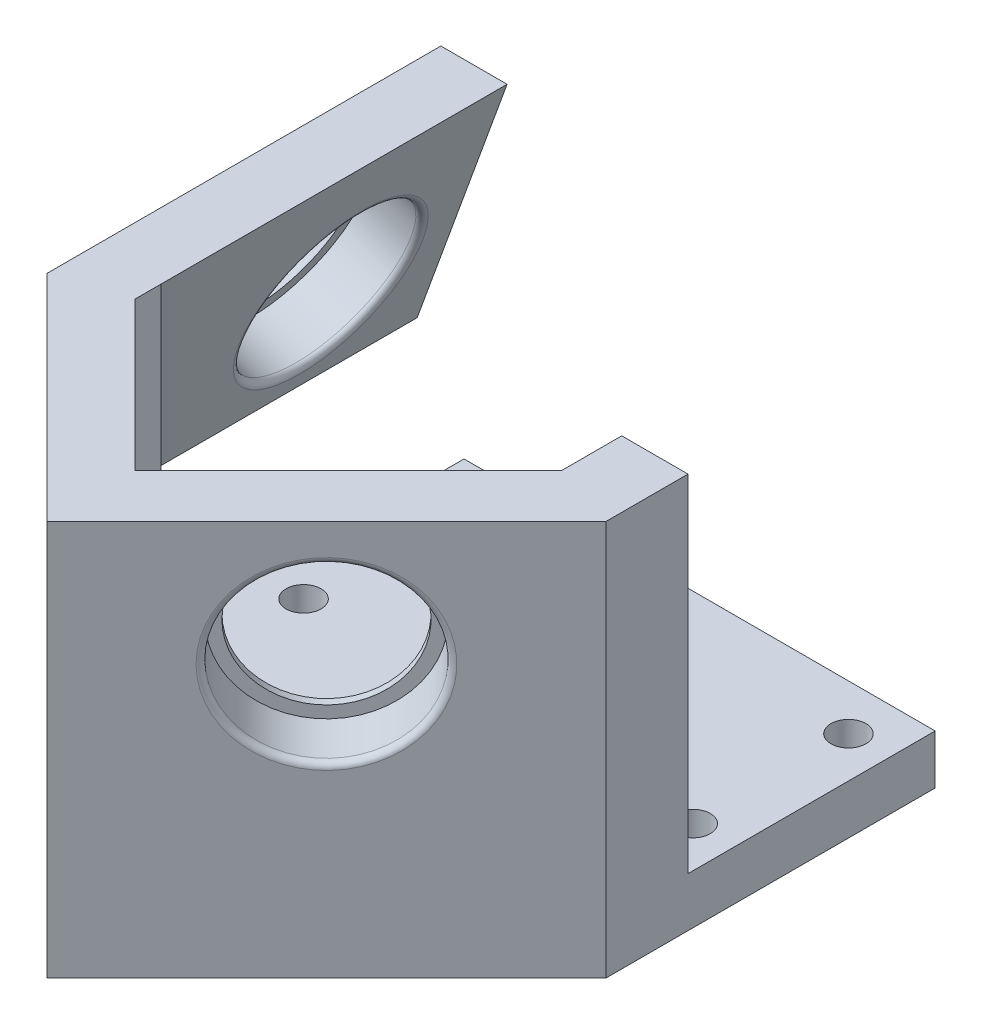
SolidWorks part; units mm, degrees
ref_plane "Front Plane" through (0, 0, 0) normal (0, 0, 1) x (1, 0, 0)
ref_plane "Top Plane" through (0, 0, 0) normal (0, 1, 0) x (1, 0, 0)
ref_plane "Right Plane" through (0, 0, 0) normal (1, 0, 0) x (0, 0, -1)
sketch "Sketch1" plane through (0, 0, 0) normal (0, 1, 0) x (1, 0, 0)
  line L0 (-35.921, 0) -> (0, 35.921)
  line L1 (-35.921, 0) -> (0, -35.921)
  line L2 (0, 35.921) -> (35.921, 0)
  line L3 (0, -35.921) -> (35.921, 0)
  line L4 (-35.921, 0) -> (35.921, 0) construction
  line L5 (0, 35.921) -> (0, -35.921) construction
  point P1 (0, 0)
  dimension "D1" = 50.8
  dimension "D2" = 50.8
extrude "Boss-Extrude1" add sketch "Sketch1" along normal mid plane 31.75
sketch "Sketch2" plane through (17.9605, 0, 17.9605) normal (0.7071, 0, 0.7071) x (0.7071, 0, -0.7071)
  circle A0 centre (0, 0) radius 11.05
  dimension "D1" = 22.1
extrude "Cut-Extrude1" cut sketch "Sketch2" against normal blind 8
sketch "Sketch3" plane through (-17.9605, 0, 17.9605) normal (-0.7071, 0, 0.7071) x (0.7071, 0, 0.7071)
  circle A0 centre (0, 0) radius 11.05
  dimension "D1" = 22.1
extrude "Cut-Extrude2" cut sketch "Sketch3" against normal blind 8
sketch "Sketch4" plane through (0, 15.875, 0) normal (0, 1, 0) x (1, 0, 0)
  line L0 (25.4, 10.521) -> (-25.4, 10.521)
  line L1 (35.921, 0) -> (0, 35.921) construction
  line L2 (0, 35.921) -> (-35.921, 0) construction
  line L3 (-25.4, 10.521) -> (0, 35.921)
  line L4 (0, 35.921) -> (25.4, 10.521)
  dimension "D1" = 25.4
extrude "Cut-Extrude3" cut sketch "Sketch4" against normal through all
sketch "Sketch5" plane through (0, 0, -10.521) normal (0, 0, -1) x (-1, 0, 0)
  line L0 (-35.921, 15.875) -> (-35.921, -15.875)
  line L1 (-35.921, -15.875) -> (39.135, -15.875)
  line L2 (39.135, -15.875) -> (27.579, 15.875)
  line L3 (27.579, 15.875) -> (-35.921, 15.875)
  line L4 (25.4, -15.875) -> (-25.4, -15.875) construction
  line L5 (-35.921, 15.875) -> (-35.921, -15.875) construction
  line L8 (25.4, 15.875) -> (-25.4, 15.875) construction
  point P6 (0, 0)
  dimension "D1" = 70
  dimension "D2" = 63.5
extrude "Boss-Extrude2" add sketch "Sketch5" against normal up to surface and the other way blind 31.75 up to face at (30.6605, 0, -5.2605)
sketch "Sketch6" plane through (-29.455, 10.7207, 0) normal (-0.9397, 0.342, 0) x (0, 0, 1)
  line L0 (-42.271, -28.3026) -> (-42.271, 5.4851) construction
  line L1 (-42.271, -28.3026) -> (-10.521, -28.3026) construction
  circle A0 centre (-26.396, -11.4088) radius 11.05
  point P4 (-42.271, -11.4088)
  point P7 (-26.396, -28.3026)
  dimension "D1" = 22.1
extrude "Cut-Extrude4" cut sketch "Sketch6" against normal through all
sketch "Sketch7" plane through (0, 0, -42.271) normal (0, 0, -1) x (-1, 0, 0)
  line L1 (-35.921, -15.875) -> (39.135, -15.875) construction
  line L3 (19.0656, 15.875) -> (30.6216, -15.875)
  line L4 (-35.921, -15.875) -> (30.6216, -15.875)
  line L5 (39.135, -15.875) -> (27.579, 15.875) construction
  line L6 (27.579, 15.875) -> (-35.921, 15.875) construction
  line L7 (-35.921, -15.875) -> (-35.921, 15.875)
  line L8 (-35.921, 15.875) -> (19.0656, 15.875)
  dimension "D3" = 8
extrude "Cut-Extrude5" cut sketch "Sketch7" against normal blind 31.75
sketch "Sketch8" plane through (0, 15.875, 0) normal (0, 1, 0) x (1, 0, 0)
  line L5 (-42.1413, -6.2203) -> (-8.2965, -39.8855)
  line L6 (0, -35.921) -> (0, -57.0039)
  line L13 (0, -57.0039) -> (-46.5861, -10.6651)
  line L14 (-46.5861, -10.6651) -> (-42.1413, -6.2203)
  line L15 (-8.2965, -39.8855) -> (-8.2965, -27.6245)
  line L16 (-35.921, 0) -> (0, -35.921) construction
  line L17 (-8.2965, -27.6245) -> (0, -35.921)
  line L18 (-25.4, 10.521) -> (-35.921, 0) construction
extrude "Boss-Extrude3" [suppressed] add sketch "Sketch8" against normal up to surface (25.4 mm away) up to face at (2.1042, -15.875, 2.9758)
sketch "Sketch9" plane through (0, -15.875, 0) normal (0, -1, 0) x (1, 0, 0)
  line L0 (-25.4, -10.521) -> (-35.921, 0)
  line L1 (-35.921, 0) -> (-46.442, -10.521)
  line L2 (-46.442, -10.521) -> (-25.4, -10.521)
  line L3 (-35.921, 0) -> (0, 35.921) construction
extrude "Boss-Extrude4" add sketch "Sketch9" against normal up to surface (31.75 mm away) up to face at (-9.1964, 15.875, -10.0783)
sketch "Sketch10" plane through (0, 0, -42.271) normal (0, 0, -1) x (-1, 0, 0)
  line L0 (39.135, -15.875) -> (27.579, 15.875) construction
  line L1 (39.135, -15.875) -> (27.579, 15.875)
  line L6 (27.579, 15.875) -> (39.135, -15.875)
  line L7 (39.135, -15.875) -> (46.442, -15.875)
  line L8 (46.442, -15.875) -> (46.442, 15.875)
  line L9 (46.442, 15.875) -> (27.579, 15.875)
  line L10 (27.579, 15.875) -> (39.135, -15.875)
  line L11 (39.135, -15.875) -> (46.442, -15.875)
  line L12 (46.442, -15.875) -> (46.442, 15.875)
  line L13 (46.442, 15.875) -> (27.579, 15.875)
  line M7 (39.135, -15.875) -> (27.579, 15.875)
  dimension "D1" = 0
extrude "Cut-Extrude6" cut sketch "Sketch10" against normal through all contours L12 L13 L11 M7 region at (-39.4743, 2.3367, -42.271)
sketch "Sketch11" plane through (0, -15.875, 0) normal (0, -1, 0) x (1, 0, 0)
  line L3 (-30.6216, -10.521) -> (-39.135, -10.521)
  line L4 (-39.135, -42.271) -> (-39.135, -3.214) construction
  line L5 (-39.135, -10.521) -> (-39.135, -3.214)
  line L10 (0, 35.921) -> (-39.135, -3.214)
  line L11 (-39.135, -3.214) -> (-39.135, -42.271)
  line L12 (-39.135, -42.271) -> (-30.6216, -42.271)
  line L13 (-30.6216, -42.271) -> (-30.6216, -10.521)
  line L21 (-30.6216, -10.521) -> (35.921, -10.521)
  line L22 (35.921, -10.521) -> (35.921, 0)
  line L23 (35.921, 0) -> (0, 35.921)
  line L24 (0, 35.921) -> (-39.135, -3.214)
  line L29 (-30.6216, -10.521) -> (35.921, -10.521)
  line L30 (35.921, -10.521) -> (35.921, 0)
  line L31 (35.921, 0) -> (0, 35.921)
  dimension "D1" = 0
extrude "Boss-Extrude5" add sketch "Sketch11" along normal blind 12.7
sketch "Sketch12" plane through (0, -28.575, 0) normal (0, -1, 0) x (1, 0, 0)
  line L0 (35.921, -10.521) -> (35.921, 0)
  line L1 (35.921, 0) -> (0, 35.921)
  line L2 (0, 35.921) -> (-39.135, -3.214)
  line L3 (-39.135, -3.214) -> (-39.135, -42.271)
  line L4 (-39.135, -42.271) -> (35.921, -42.271)
  line L5 (35.921, -42.271) -> (35.921, -10.521)
extrude "Boss-Extrude6" add sketch "Sketch12" along normal blind 6.35
sketch "Sketch14" plane through (0, 0, -10.521) normal (0, 0, -1) x (-1, 0, 0)
  line L0 (35.244, -28.575) -> (19.0656, 15.875)
  line L1 (39.135, -34.925) -> (26.3581, -34.925)
  line L2 (19.0656, 15.875) -> (8.4238, 15.875)
  line L3 (24.6023, -28.575) -> (8.4238, 15.875)
  line L4 (19.0656, 15.875) -> (-35.921, 15.875) construction
  line L5 (30.6216, -15.875) -> (19.0656, 15.875) construction
  line L6 (39.135, -34.925) -> (-35.921, -34.925) construction
  line L7 (39.135, -34.925) -> (39.135, -28.575)
  line L8 (39.135, -28.575) -> (35.244, -28.575)
  line L9 (24.6023, -28.575) -> (24.6023, -34.925)
  line L10 (24.6023, -34.925) -> (26.3581, -34.925)
  line L11 (39.135, -28.575) -> (-35.921, -28.575) construction
  dimension "D1" = 10
extrude "Cut-Extrude7" cut sketch "Sketch14" along normal through all
sketch "Sketch15" plane through (0, -34.925, 0) normal (0, -1, 0) x (1, 0, 0)
  line L0 (-24.6023, -42.271) -> (35.921, -42.271) construction
  line L1 (30.6594, -16.396) -> (-19.3406, -16.396) construction
  line L2 (30.6594, -16.396) -> (30.6594, -36.396) construction
  line L3 (30.6594, -36.396) -> (-19.3406, -36.396) construction
  line L4 (-19.3406, -16.396) -> (-19.3406, -36.396) construction
  line L5 (30.6594, -16.396) -> (-19.3406, -36.396) construction
  line L6 (30.6594, -36.396) -> (-19.3406, -16.396) construction
  line L9 (-24.6023, -42.271) -> (-24.6023, -10.521) construction
  circle A0 centre (30.6594, -36.396) radius 2.25
  circle A1 centre (30.6594, -16.396) radius 2.25
  circle A2 centre (-19.3406, -16.396) radius 2.25
  circle A3 centre (-19.3406, -36.396) radius 2.25
  point P0 (5.6594, -26.396)
  point P11 (5.6594, -42.271)
  point P14 (-24.6023, -26.396)
  dimension "D1" = 4.5
  dimension "D2" = 50
  dimension "D3" = 20
extrude "Cut-Extrude8" cut sketch "Sketch15" against normal up to next
sketch "Sketch22" plane through (-29.455, 10.7207, 0) normal (-0.9397, 0.342, 0) x (0, 0, 1)
  circle A0 centre (-26.396, -11.4088) radius 9.5
  circle A1 centre (-26.396, -11.4088) radius 11.05 construction
  circle A2 centre (-26.396, -11.4088) radius 11.05
  dimension "D1" = 19
extrude "Boss-Extrude10" add sketch "Sketch22" against normal offset from surface (1 mm away) 7 up to face at (-24.8436, 0, -26.396)
fillet "Fillet1" radius 0.7937 3 edges at (25.774, 0, 10.147) (-10.147, 0, 25.774) (-29.6188, -13.1198, -26.396)
sketch "Sketch17" plane through (0, 15.875, 0) normal (0, 1, 0) x (1, 0, 0)
  line L0 (-19.0656, 10.521) -> (-19.0656, -5.5418)
  line L1 (-19.0656, -5.5418) -> (0, -24.6073)
  line L2 (0, -24.6073) -> (27.4076, 2.8003)
  line L3 (27.4076, 2.8003) -> (27.4076, 10.521)
  line L4 (-19.0656, 10.521) -> (35.921, 10.521) construction
  line L5 (13.7038, -10.9035) -> (19.3607, -16.5604) construction
  line L6 (0, -35.921) -> (35.921, 0) construction
  line L7 (-9.5328, -15.0745) -> (-15.1896, -20.7314) construction
  line L8 (-27.579, -8.342) -> (0, -35.921) construction
  line L9 (27.4076, 10.521) -> (35.921, 10.521) construction
  line L10 (-19.0656, 10.521) -> (-27.579, 10.521) construction
  line L11 (-27.579, 42.271) -> (-27.579, -8.342) construction
  line L12 (-19.0656, 10.521) -> (27.4076, 10.521)
  dimension "D1" = 8
extrude "Cut-Extrude9" cut sketch "Sketch17" against normal up to surface (44.45 mm away) up to face at (-19.3406, -28.575, -34.146)
sketch "Sketch18" plane through (-12.3037, 0, 12.3037) normal (0.7071, 0, -0.7071) x (-0.7071, 0, -0.7071)
  circle A0 centre (0, 0) radius 9.5
  arc A1 (9.5628, 5.5368) -> (9.5628, -5.5368) centre (0, 0) ccw construction
  arc A2 (9.5628, 5.5368) -> (9.5628, -5.5368) centre (0, 0) ccw
  arc A3 (9.5628, 5.5368) -> (9.5628, -5.5368) centre (0, 0) cw
  dimension "D1" = 19
extrude "Boss-Extrude8" add sketch "Sketch18" against normal offset from surface (1 mm away) 7 up to face at (-26.3353, 0, 9.5857)
sketch "Sketch19" plane through (12.3037, 0, 12.3037) normal (-0.7071, 0, -0.7071) x (-0.7071, 0, 0.7071)
  circle A0 centre (0, 0) radius 9.5
  circle A1 centre (0, 0) radius 11.05 construction
  circle A2 centre (0, 0) radius 11.05
  dimension "D1" = 19
extrude "Boss-Extrude9" add sketch "Sketch19" against normal offset from surface (1 mm away) 7 up to face at (9.5857, 0, 26.3353)
sketch "Sketch20" plane through (0, 0, -10.521) normal (0, 0, -1) x (-1, 0, 0)
  line L7 (30.6216, -15.875) -> (19.0656, 15.875)
  line L8 (19.0656, 15.875) -> (19.0656, -28.575)
  line L9 (19.0656, -28.575) -> (24.6023, -28.575)
  line L10 (24.6023, -28.575) -> (24.6023, -34.925)
  line L11 (24.6023, -34.925) -> (39.135, -34.925)
  line L12 (39.135, -34.925) -> (39.135, -15.875)
  line L13 (39.135, -15.875) -> (30.6216, -15.875)
  line L14 (30.6216, -15.875) -> (19.0656, 15.875)
  line L15 (19.0656, 15.875) -> (19.0656, -28.575)
  line L16 (19.0656, -28.575) -> (24.6023, -28.575)
  line L17 (24.6023, -28.575) -> (24.6023, -34.925)
  line L18 (24.6023, -34.925) -> (39.135, -34.925)
  line L19 (39.135, -34.925) -> (39.135, -15.875)
  line L20 (39.135, -15.875) -> (30.6216, -15.875)
  dimension "D1" = 0
extrude "Cut-Extrude10" cut sketch "Sketch20" against normal blind 12.7
sketch "Sketch21" plane through (0, 0, 2.179) normal (0, 0, -1) x (-1, 0, 0)
  line L0 (24.6023, -28.575) -> (24.6023, -34.925) construction
  line L1 (33.742, -34.925) -> (24.6023, -34.925)
  line L2 (33.742, -34.925) -> (33.742, -15.875)
  line L3 (33.742, -15.875) -> (24.6023, -15.875)
  line L4 (24.6023, -34.925) -> (24.6023, -15.875)
  line L5 (33.742, -15.875) -> (30.6216, -15.875) construction
extrude "Cut-Extrude11" cut sketch "Sketch21" against normal through all
